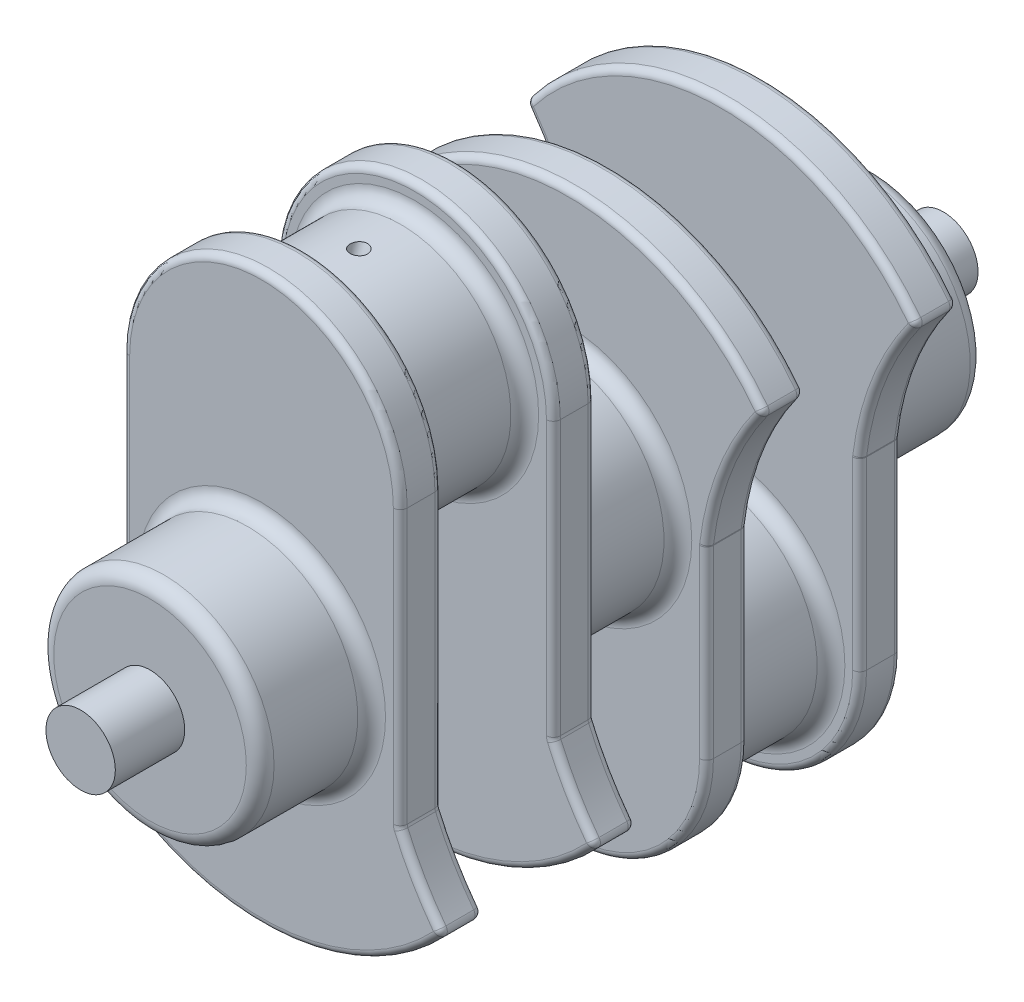
SolidWorks part; units mm, degrees
material "AISI 4340 Steel, normalized"
ref_plane "Front Plane" through (0, 0, 0) normal (0, 0, 1) x (1, 0, 0)
ref_plane "Top Plane" through (0, 0, 0) normal (0, 1, 0) x (1, 0, 0)
ref_plane "Right Plane" through (0, 0, 0) normal (1, 0, 0) x (0, 0, -1)
sketch "Sketch1" plane through (0, 0, 0) normal (0, 0, 1) x (1, 0, 0)
  circle A0 centre (0, 0) radius 31.75
  dimension "D1" = 31.75
extrude "Boss-Extrude1" add sketch "Sketch1" along normal blind 32.13
sketch "Sketch8" plane through (0, 0, 0) normal (0, 0, -1) x (-1, 0, 0)
  line L0 (-40, 53.333) -> (-40, -25.971)
  line L1 (40, 53.333) -> (40, -25.971)
  arc A0 (40, 53.333) -> (-40, 53.333) centre (0, 53.333) ccw
  arc A5 (-52.1591, -46.6843) -> (52.1591, -46.6843) centre (0, 0) ccw
  arc A6 (-40, -25.971) -> (-52.1591, -46.6843) centre (-125, 10) cw
  arc A7 (40, -25.971) -> (52.1591, -46.6843) centre (125, 10) ccw
  dimension "D1" = 40
  dimension "D2" = 70
  dimension "D3" = 53.333
  dimension "D5" = 10
  dimension "D6" = 125
extrude "Boss-Extrude5" add sketch "Sketch8" along normal blind 12
sketch "Sketch2" plane through (0, 0, 32.13) normal (0, 0, 1) x (1, 0, 0)
  circle A0 centre (0, 0) radius 10
  dimension "D1" = 10
extrude "Boss-Extrude2" add sketch "Sketch2" along normal blind 20
sketch "Sketch9" plane through (0, 0, -12) normal (0, 0, -1) x (-1, 0, 0)
  circle A0 centre (0, 53.333) radius 31.75
  dimension "D2" = 31.75
  dimension "D1" = 53.333
extrude "Boss-Extrude6" add sketch "Sketch9" along normal blind 32.13
ref_plane "Plane4" through (0, 0, -88.26) normal (0, 0, -1) x (-1, 0, 0)
sketch "Sketch10" plane through (0, 0, -44.13) normal (0, 0, -1) x (-1, 0, 0)
  line L0 (-40, -53.333) -> (-40, 0)
  line L1 (40, -53.333) -> (40, 0)
  arc A0 (-40, -53.333) -> (40, -53.333) centre (0, -53.333) ccw
  arc A1 (-40, 0) -> (-56.5054, 41.3175) centre (-125, -10) ccw
  arc A2 (40, 0) -> (56.5054, 41.3175) centre (125, -10) cw
  arc A3 (-56.5054, 41.3175) -> (56.5054, 41.3175) centre (0, 0) cw
  dimension "D1" = 40
  dimension "D5" = 10
  dimension "D3" = 70
  dimension "D2" = 53.333
  dimension "D4" = 125
extrude "Boss-Extrude7" add sketch "Sketch10" along normal blind 12 from surface starting at plane "Plane4"
ref_plane "Plane3" through (0, 0, -132.39) normal (0, 0, -1) x (-1, 0, 0)
sketch "Sketch12" plane through (0, 0, -132.39) normal (0, 0, -1) x (-1, 0, 0)
  line L2 (40, -53.333) -> (40, 0)
  line L3 (40, -53.333) -> (40, 0)
  line L4 (-40, 0) -> (-40, -53.333)
  line L5 (-40, 0) -> (-40, -53.333)
  arc A12 (-40, -53.333) -> (40, -53.333) centre (0, -53.333) ccw
  arc A13 (56.5054, 41.3175) -> (40, 0) centre (125, -10) ccw
  arc A14 (56.5054, 41.3175) -> (-56.5054, 41.3175) centre (0, 0) ccw
  arc A15 (-40, 0) -> (-56.5054, 41.3175) centre (-125, -10) ccw
  arc A16 (-40, -53.333) -> (40, -53.333) centre (0, -53.333) ccw
  arc A17 (56.5054, 41.3175) -> (40, 0) centre (125, -10) ccw
  arc A18 (56.5054, 41.3175) -> (-56.5054, 41.3175) centre (0, 0) ccw
  arc A19 (-40, 0) -> (-56.5054, 41.3175) centre (-125, -10) ccw
  dimension "D1" = 0
extrude "Boss-Extrude8" add sketch "Sketch12" along normal blind 12
sketch "Sketch14" plane through (0, 0, -100.26) normal (0, 0, -1) x (-1, 0, 0)
  circle A0 centre (0, -53.333) radius 31.75
  dimension "D2" = 31.75
  dimension "D1" = 53.333
extrude "Boss-Extrude9" add sketch "Sketch14" along normal up to next
sketch "Sketch15" plane through (0, 0, -144.39) normal (0, 0, -1) x (-1, 0, 0)
  circle A1 centre (0, 0) radius 31.75
  circle A2 centre (0, 0) radius 31.75
  dimension "D1" = 0
extrude "Boss-Extrude10" add sketch "Sketch15" along normal blind 32.13
sketch "Sketch16" plane through (0, 0, -176.52) normal (0, 0, -1) x (-1, 0, 0)
  circle A1 centre (0, 0) radius 10
  circle A2 centre (0, 0) radius 10
  dimension "D1" = 0
extrude "Boss-Extrude11" add sketch "Sketch16" along normal blind 20
sketch "Sketch18" plane through (0, 0, -44.13) normal (0, 0, -1) x (-1, 0, 0)
  line L2 (-40, 53.333) -> (-40, -25.971)
  line L3 (-40, 53.333) -> (-40, -25.971)
  line L4 (40, -25.971) -> (40, 53.333)
  line L5 (40, -25.971) -> (40, 53.333)
  arc A4 (40, 53.333) -> (-40, 53.333) centre (0, 53.333) ccw
  arc A5 (-52.1591, -46.6843) -> (-40, -25.971) centre (-125, 10) ccw
  arc A6 (-52.1591, -46.6843) -> (52.1591, -46.6843) centre (0, 0) ccw
  arc A7 (40, -25.971) -> (52.1591, -46.6843) centre (125, 10) ccw
  arc A8 (40, 53.333) -> (-40, 53.333) centre (0, 53.333) ccw
  arc A9 (-52.1591, -46.6843) -> (-40, -25.971) centre (-125, 10) ccw
  arc A10 (-52.1591, -46.6843) -> (52.1591, -46.6843) centre (0, 0) ccw
  arc A11 (40, -25.971) -> (52.1591, -46.6843) centre (125, 10) ccw
  dimension "D1" = 0
extrude "Boss-Extrude12" add sketch "Sketch18" along normal blind 12
sketch "Sketch19" plane through (0, 0, -56.13) normal (0, 0, -1) x (-1, 0, 0)
  circle A1 centre (0, 0) radius 31.75
  circle A2 centre (0, 0) radius 31.75
  dimension "D1" = 0
extrude "Boss-Extrude13" add sketch "Sketch19" along normal up to next
fillet "Fillet1" radius 2 32 edges at (0, -70, -44.13) (-45.4029, -36.7249, -44.13) (-40, 13.681, -44.13) (40, 13.681, -44.13) (45.4029, -36.7249, -44.13) (0, -70, -56.13) (-45.4029, -36.7249, -56.13) (-40, 13.681, -56.13) (0, 93.333, -56.13) (40, 13.681, -56.13) (45.4029, -36.7249, -56.13) (52.1591, -46.6843, -50.13) (40, -25.971, -50.13) (-40, -25.971, -50.13) (-52.1591, -46.6843, -50.13) (0, 93.333, -44.13) (40, 13.681, 0) (45.4029, -36.7249, 0) (0, -70, 0) (-45.4029, -36.7249, 0) (-40, 13.681, 0) (0, 93.333, -12) (40, 13.681, -12) (45.4029, -36.7249, -12) (0, -70, -12) (-45.4029, -36.7249, -12) (-40, 13.681, -12) (-40, -25.971, -6) (-52.1591, -46.6843, -6) (52.1591, -46.6843, -6) (40, -25.971, -6) (0, 93.333, 0)
fillet "Fillet2" radius 2 16 edges at (0, 70, -132.39) (45.5209, 21.7501, -132.39) (40, -26.6665, -132.39) (0, -93.333, -132.39) (-40, -26.6665, -132.39) (-45.5209, 21.7501, -132.39) (45.5209, 21.7501, -144.39) (40, -26.6665, -144.39) (0, -93.333, -144.39) (-40, -26.6665, -144.39) (-45.5209, 21.7501, -144.39) (-56.5054, 41.3175, -138.39) (-40, 0, -138.39) (40, 0, -138.39) (56.5054, 41.3175, -138.39) (0, 70, -144.39)
fillet "Fillet3" radius 2 16 edges at (40, -26.6665, -88.26) (45.5209, 21.7501, -88.26) (0, 70, -88.26) (-45.5209, 21.7501, -88.26) (-40, -26.6665, -88.26) (0, -93.333, -88.26) (40, -26.6665, -100.26) (45.5209, 21.7501, -100.26) (-45.5209, 21.7501, -100.26) (-40, -26.6665, -100.26) (0, -93.333, -100.26) (40, 0, -94.26) (56.5054, 41.3175, -94.26) (-56.5054, 41.3175, -94.26) (-40, 0, -94.26) (0, 70, -100.26)
fillet "Fillet5" radius 4 2 edges at (31.75, 0, 32.13) (31.75, 0, 0)
fillet "Fillet6" radius 4 2 edges at (-31.75, 0, -144.39) (-31.75, 0, -176.52)
ref_plane "Plane5" through (0, 31.75, 0) normal (0, 1, 0) x (1, 0, 0)
sketch "Sketch20" plane through (0, 0, 0) normal (1, 0, 0) x (0, 0, -1)
  line L1 (100.26, -85.083) -> (100.26, -21.583)
  line L2 (100.26, -85.083) -> (100.26, -21.583)
  dimension "D1" = 0
ref_plane "Plane6" through (0, -85.083, 0) normal (0, 1, 0) x (1, 0, 0)
sketch "Sketch21" plane through (0, 31.75, 0) normal (0, 1, 0) x (1, 0, 0)
  line L2 (-31.75, 172.52) -> (31.75, 172.52) construction
  line L3 (-31.75, 172.52) -> (-31.75, 148.39) construction
  line L4 (-31.75, 148.39) -> (31.75, 148.39) construction
  line L5 (31.75, 172.52) -> (31.75, 148.39) construction
  circle A0 centre (0, 160.455) radius 2.5
  point P10 (0, 172.52)
  point P11 (31.75, 160.455)
  dimension "D1" = 5
sketch "Sketch27" plane through (0, 0, 0) normal (0, 0, 1) x (1, 0, 0)
  line L0 (0, 85.083) -> (0, -31.75) construction
  circle A1 centre (0, 53.333) radius 31.75
  circle A2 centre (0, 53.333) radius 31.75 construction
  circle A3 centre (0, 0) radius 31.75
  circle A4 centre (0, 0) radius 31.75 construction
  dimension "D1" = 0
  dimension "D2" = 0
ref_plane "Plane8" through (0, 85.083, 0) normal (0, -1, 0) x (-1, 0, 0)
ref_plane "Plane9" through (0, -31.75, 0) normal (0, -1, 0) x (-1, 0, 0)
sketch "Sketch28" plane through (0, -31.75, 0) normal (0, -1, 0) x (-1, 0, 0)
  line L1 (-31.75, -4) -> (31.75, -4) construction
  line L2 (-31.75, -4) -> (-31.75, -28.13) construction
  line L3 (-31.75, -28.13) -> (31.75, -28.13) construction
  line L4 (31.75, -4) -> (31.75, -28.13) construction
  line L5 (-31.75, -4) -> (31.75, -28.13) construction
  line L6 (-31.75, -28.13) -> (31.75, -4) construction
  circle A0 centre (0, -16.065) radius 2.5
  point P4 (0, -16.065)
  dimension "D1" = 5
sketch "Sketch29" plane through (0, 85.083, 0) normal (0, -1, 0) x (-1, 0, 0)
  line L1 (31.75, 44.13) -> (-31.75, 44.13) construction
  line L2 (31.75, 44.13) -> (31.75, 12) construction
  line L3 (31.75, 12) -> (-31.75, 12) construction
  line L4 (-31.75, 44.13) -> (-31.75, 12) construction
  line L5 (31.75, 44.13) -> (-31.75, 12) construction
  line L6 (31.75, 12) -> (-31.75, 44.13) construction
  circle A0 centre (0, 28.065) radius 2.5
  point P4 (0, 28.065)
sketch "Sketch31" plane through (0, 0, 0) normal (1, 0, 0) x (0, 0, -1)
  line L0 (28.065, 85.083) -> (-16.065, -31.75) construction
ref_plane "Plane10" through (0, 85.083, -28.065) normal (0, -0.9355, 0.3534) x (-1, 0, 0)
ref_plane "Plane11" through (0, -31.75, 16.065) normal (0, -0.9355, 0.3534) x (-1, 0, 0)
combine bodies "Combine1" operation type add bodies to combine 119 109 117
fillet "Fillet7" radius 4 6 edges at (-31.75, 53.333, -44.13) (-31.75, 53.333, -12) (-31.75, 0, -56.13) (-31.75, 0, -88.26) (-31.75, -53.333, -132.39) (-31.75, -53.333, -100.26)
sketch "Sketch39" plane through (0, -85.083, 0) normal (0, 1, 0) x (1, 0, 0)
  line L1 (31.75, 128.39) -> (-31.75, 128.39) construction
  line L2 (31.75, 128.39) -> (31.75, 104.26) construction
  line L3 (31.75, 104.26) -> (-31.75, 104.26) construction
  line L4 (-31.75, 128.39) -> (-31.75, 104.26) construction
  line L5 (31.75, 128.39) -> (-31.75, 104.26) construction
  line L6 (31.75, 104.26) -> (-31.75, 128.39) construction
  point P4 (0, 116.325)
sketch "Sketch40" plane through (0, 0, 0) normal (1, 0, 0) x (0, 0, -1)
  line L0 (160.455, 31.75) -> (116.325, -85.083) construction
  line L1 (172.52, 31.75) -> (148.39, 31.75) construction
ref_plane "Plane12" through (0, 31.75, -160.455) normal (0, -0.9355, 0.3534) x (-1, 0, 0)
ref_plane "Plane13" through (0, -85.083, -116.325) normal (0, -0.9355, 0.3534) x (-1, 0, 0)
sketch "Sketch47" plane through (0, 85.083, -28.065) normal (0, -0.9355, 0.3534) x (-1, 0, 0)
  ellipse E0 centre (0, 0) end of major axis (2.5, 0) minor radius 2.3387 construction
  ellipse E1 centre (0, 0) end of major axis (2.5, 0) minor radius 2.3387
extrude "Cut-Extrude1" cut sketch "Sketch47" along normal through all
sketch "Sketch48" plane through (0, -31.75, 16.065) normal (0, -0.9355, 0.3534) x (-1, 0, 0)
  ellipse E0 centre (0, 0) end of major axis (2.5, 0) minor radius 2.3387 construction
  ellipse E1 centre (0, 0) end of major axis (2.5, 0) minor radius 2.3387
extrude "Cut-Extrude2" cut sketch "Sketch48" against normal through all
sketch "Sketch49" plane through (0, -85.083, -116.325) normal (0, -0.9355, 0.3534) x (-1, 0, 0)
  circle A0 centre (0, 0) radius 2.5
  dimension "D1" = 5
extrude "Cut-Extrude3" cut sketch "Sketch49" against normal through all
sketch "Sketch50" plane through (0, 31.75, -160.455) normal (0, -0.9355, 0.3534) x (-1, 0, 0)
  circle A0 centre (0, 0) radius 2.5 construction
  circle A1 centre (0, 0) radius 2.5
extrude "Cut-Extrude4" cut sketch "Sketch50" along normal through all
equation "\"CRR\"= 53.333mm'Crank Radius"
equation "\"D1@Sketch9\"=\"CRR\""
equation "\"D1@Sketch14\"=\"CRR\""
equation "\"JR\"= 31.75mm'Journal Radius"
equation "\"D1@Sketch1\"=\"JR\""
equation "\"D2@Sketch9\"=\"JR\""
equation "\"D2@Sketch14\"=\"JR\""
equation "\"LT\"= 12mm'Lobe Thickness"
equation "\"D1@Boss-Extrude5\"=\"LT\""
equation "\"D1@Boss-Extrude7\"=\"LT\""
equation "\"D1@Boss-Extrude8\"=\"LT\""
equation "\"D1@Boss-Extrude12\"=\"LT\""
equation "\"D3@Sketch8\"=\"CRR\""
equation "\"D2@Sketch10\"=\"CRR\""
equation "\"JL\"= 24.13 + 2 * ( \"JF\" )'Journal Length"
equation "\"D1@Boss-Extrude1\"=\"JL\""
equation "\"D1@Boss-Extrude6\"=\"JL\""
equation "\"D1@Boss-Extrude10\"=\"JL\""
equation "\"LHD\"= 5mm'Lubrication Hole Diameter"
equation "\"D1@Sketch29\"=\"LHD\""
equation "\"JF\"= 4mm'Internal Journal Fillets"
equation "\"D1@Fillet7\"=\"JF\""
equation "\"D1@Fillet6\"=\"JF\""
equation "\"LR\" = 40mm'Lobe radius"
equation "\"CWR\" = 70mm'Counterweight Radius"
equation "\"D1@Sketch8\"=\"LR\""
equation "\"D2@Sketch8\"=\"CWR\""
equation "\"D3@Sketch10\"=\"CWR\""
equation "\"D1@Sketch10\"=\"LR\""
